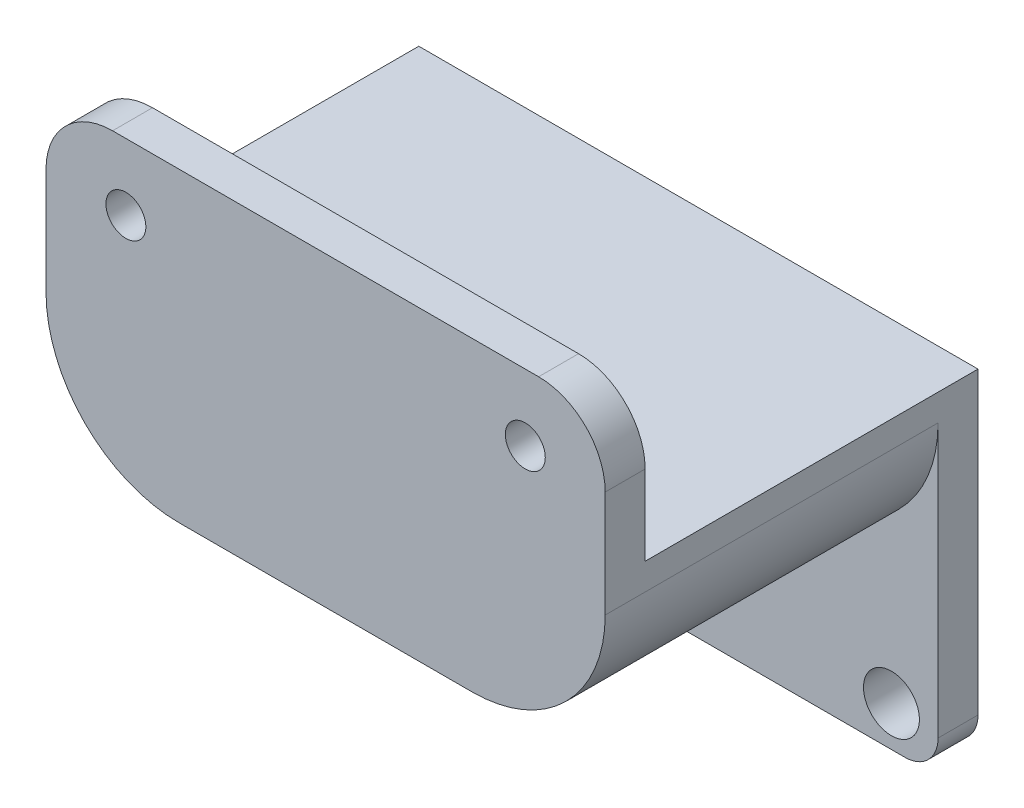
SolidWorks part; units mm, degrees
ref_plane "Front Plane" through (0, 0, 0) normal (0, 0, 1) x (1, 0, 0)
ref_plane "Top Plane" through (0, 0, 0) normal (0, 1, 0) x (1, 0, 0)
ref_plane "Right Plane" through (0, 0, 0) normal (1, 0, 0) x (0, 0, -1)
sketch "Sketch3" plane through (0, 0, 0) normal (0, 0, 1) x (1, 0, 0)
  line L0 (-22.5928, 16.5094) -> (-6.0928, 16.5094)
  line L1 (-48.0928, 16.5094) -> (-31.5928, 16.5094)
  line L2 (-48.0928, 16.5094) -> (-48.0928, 3.5094)
  line L3 (-38.0928, -6.4906) -> (-16.0928, -6.4906)
  line L4 (-6.0928, 16.5094) -> (-6.0928, 3.5094)
  line L5 (-31.5928, 16.5094) -> (-22.5928, 16.5094)
  circle A1 centre (-42.0928, 11.5094) radius 1.5
  circle A2 centre (-12.0928, 11.5094) radius 1.5
  arc A3 (-48.0928, 3.5094) -> (-38.0928, -6.4906) centre (-38.0928, 3.5094) ccw
  arc A4 (-16.0928, -6.4906) -> (-6.0928, 3.5094) centre (-16.0928, 3.5094) ccw
  point P12 (-27.0928, -6.4906)
  point P16 (-48.0928, -6.4906)
  dimension "D4" = 3
  dimension "D5" = 3
  dimension "D12" = 10
  dimension "D13" = 10
  dimension "D1" = 42
  dimension "D2" = 23
  dimension "D6" = 18
  dimension "D7" = 30
  dimension "D8" = 18
  dimension "D9" = 15
  dimension "D10" = 15
extrude "Boss-Extrude3" add sketch "Sketch3" along normal blind 3
sketch "Sketch6" plane through (0, 0, 0) normal (0, 0, 1) x (1, 0, 0)
  line L2 (-48.0928, 5.5094) -> (-48.0928, 3.5094)
  line L3 (-38.0928, -6.4906) -> (-16.0928, -6.4906)
  line L4 (-6.0928, 5.5094) -> (-6.0928, 3.5094)
  line L5 (-6.0928, 5.5094) -> (-48.0928, 5.5094)
  arc A3 (-48.0928, 3.5094) -> (-38.0928, -6.4906) centre (-38.0928, 3.5094) ccw
  arc A4 (-16.0928, -6.4906) -> (-6.0928, 3.5094) centre (-16.0928, 3.5094) ccw
  dimension "D1" = 12
extrude "Boss-Extrude4" add sketch "Sketch6" against normal blind 25
ref_plane "Plane7" through (0, 5.5094, 0) normal (0, 1, 0) x (1, 0, 0)
sketch "Sketch9" plane through (0, 5.5094, 0) normal (0, 1, 0) x (1, 0, 0)
  line L0 (-48.0928, 25) -> (-48.0928, 0) construction
  line L1 (-6.0928, 25) -> (-48.0928, 25)
  line L2 (-6.0928, 25) -> (-6.0928, 22)
  line L3 (-6.0928, 22) -> (-48.0928, 22)
  line L4 (-48.0928, 25) -> (-48.0928, 22)
  dimension "D1" = 42
  dimension "D2" = 3
fillet "Fillet4" radius 5 2 edges at (-48.0928, 16.5094, 1.5) (-6.0928, 16.5094, 1.5)
extrude "Boss-Extrude7" add sketch "Sketch9" against normal blind 30
fillet "Fillet6" radius 5 1 edges at (-6.0928, -24.4906, -23.5)
fillet "Fillet7" radius 5 1 edges at (-48.0928, -24.4906, -23.5)
ref_plane "Plane13" through (0, 0, -25) normal (0, 0, -1) x (-1, 0, 0)
sketch "Sketch11" plane through (0, 0, -25) normal (0, 0, -1) x (-1, 0, 0)
  line L0 (6.0928, -19.4906) -> (6.0928, 5.5094) construction
  line L3 (22.5928, -24.4906) -> (31.5928, -24.4906)
  line L4 (48.0928, 5.5094) -> (48.0928, -19.4906) construction
  arc A0 (31.5928, -24.4906) -> (22.5928, -24.4906) centre (27.0928, -24.4906) ccw
  circle A1 centre (9.5928, -16.4906) radius 2.1
  circle A2 centre (44.5928, -16.4906) radius 2.1
  dimension "D4" = 8
  dimension "D1" = 4.2
  dimension "D2" = 35
  dimension "D3" = 17.5
  dimension "D5" = 8
  dimension "D6" = 17.5
  dimension "D7" = 21
  dimension "D8" = 21
  dimension "D9" = 3.5
  dimension "D10" = 3.5
extrude "Cut-Extrude2" cut sketch "Sketch11" against normal blind 30
sketch "Sketch12" plane through (0, 0, -25) normal (0, 0, -1) x (-1, 0, 0)
  line L2 (6.0928, -19.4906) -> (50.3785, -19.4906)
  line L3 (6.0928, -19.4906) -> (6.0928, -26.4662)
  line L4 (6.0928, -26.4662) -> (50.3785, -26.4662)
  line L5 (50.3785, -19.4906) -> (50.3785, -26.4662)
extrude "Cut-Extrude3" cut sketch "Sketch12" against normal blind 10
fillet "Fillet8" radius 2.5 2 edges at (-48.0928, -19.4906, -23.5) (-6.0928, -19.4906, -23.5)
